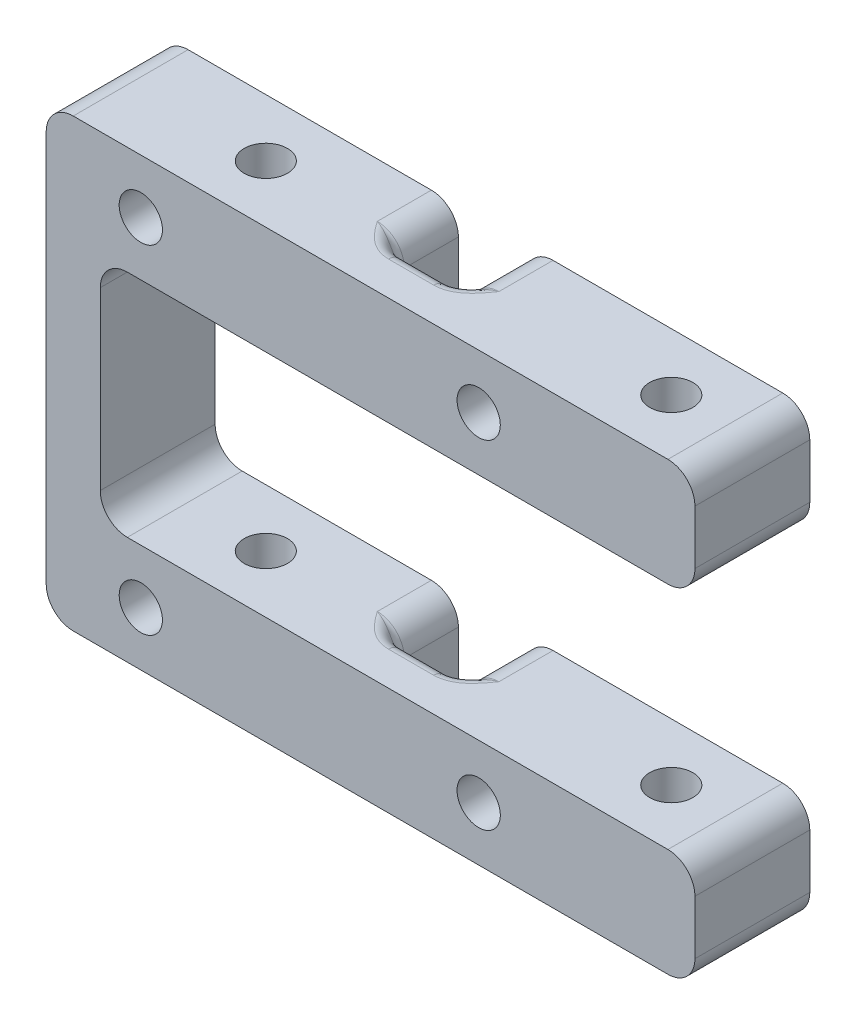
SolidWorks part; units mm, degrees
ref_plane "前视基准面" through (0, 0, 0) normal (0, 0, 1) x (1, 0, 0)
ref_plane "上视基准面" through (0, 0, 0) normal (0, 1, 0) x (1, 0, 0)
ref_plane "右视基准面" through (0, 0, 0) normal (1, 0, 0) x (0, 0, -1)
other "Configuration Table"
sketch "草图1" plane through (0, 0, 0) normal (0, 0, 1) x (1, 0, 0)
  line L1 (0, 0) -> (48, 0)
  line L2 (0, 0) -> (0, 33)
  line L3 (0, 33) -> (48, 33)
  line L4 (48, 0) -> (48, 33)
  dimension "D1" = 48
  dimension "D2" = 33
extrude "凸台-拉伸1" add sketch "草图1" along normal blind 8.5
sketch "草图2" plane through (0, 0, 8.5) normal (0, 0, 1) x (1, 0, 0)
  line L0 (0, 16.5) -> (51.2817, 16.5) construction
  line L1 (0, 33) -> (0, 0) construction
  line L2 (48, 0) -> (48, 33) construction
  line L3 (4, 16.5) -> (48, 16.5)
  line L4 (4, 8) -> (4, 25)
  line L5 (4, 25) -> (48, 25)
  line L6 (48, 8) -> (48, 25)
  line L7 (4, 8) -> (48, 8)
  line M6 (48, 0) -> (48, 33)
  dimension "D1" = 4
  dimension "D2" = 8.5
extrude "切除-拉伸1" cut sketch "草图2" against normal blind 8.5 contours L5 L4 L3 M6 | L4 L7 L3 M6 region at (26, 20.75, 8.5) region at (26, 12.25, 8.5)
sketch "草图3" plane through (0, 0, 0) normal (0, -1, 0) x (1, 0, 0)
  line L0 (0, 4.25) -> (48.3621, 4.25) construction
  line L1 (0, 8.5) -> (0, 0) construction
  circle A0 centre (12, 4.25) radius 1.6
  circle A1 centre (42, 4.25) radius 1.6
  dimension "D1" = 3.2
  dimension "D2" = 3.2
  dimension "D3" = 30
  dimension "D4" = 12
extrude "切除-拉伸2" cut sketch "草图3" against normal blind 48.5
sketch "草图4" plane through (0, 0, 0) normal (0, -1, 0) x (1, 0, 0)
  line L0 (0, 0) -> (48, 0) construction
  line L1 (22, 0) -> (27, 0)
  line L2 (22, 0) -> (22, 5)
  line L3 (22, 5) -> (27, 5)
  line L4 (27, 0) -> (27, 5)
  line L5 (0, 8.5) -> (48, 8.5) construction
  line L7 (48, 8.5) -> (48, 0) construction
  dimension "D1" = 3.5
  dimension "D2" = 5
  dimension "D3" = 21
extrude "切除-拉伸3" cut sketch "草图4" against normal blind 48.5
fillet "圆角1" radius 2 8 edges at (22, 0, 2.5) (27, 0, 2.5) (27, 25, 2.5) (27, 33, 2.5) (22, 25, 2.5) (22, 33, 2.5) (27, 8, 2.5) (22, 8, 2.5)
fillet "圆角2" radius 1 16 edges at (24.5, 33, 5) (24.5, 25, 5) (24.5, 8, 5) (24.5, 0, 5) (27.5858, 32.4142, 5) (27.5858, 25.5858, 5) (21.4142, 32.4142, 5) (21.4142, 25.5858, 5) (27.5858, 7.4142, 5) (27.5858, 0.5858, 5) (21.4142, 7.4142, 5) (21.4142, 0.5858, 5) (27, 29, 5) (22, 29, 5) (27, 4, 5) (22, 4, 5)
fillet "圆角3" radius 2 8 edges at (4, 25, 4.25) (4, 8, 4.25) (48, 8, 4.25) (0, 0, 4.25) (0, 33, 4.25) (48, 33, 4.25) (48, 25, 4.25) (48, 0, 4.25)
sketch "草图5" plane through (0, 0, 8.5) normal (0, 0, 1) x (1, 0, 0)
  line L0 (0, 16.5) -> (50.5462, 16.5) construction
  line L1 (0, 31) -> (0, 2) construction
  circle A0 centre (32, 29) radius 1.6
  circle A1 centre (7, 29) radius 1.6
  circle A2 centre (7, 4) radius 1.6
  circle A3 centre (32, 4) radius 1.6
  dimension "D1" = 3.2
  dimension "D2" = 12.5
  dimension "D4" = 7
  dimension "D3" = 2
extrude "切除-拉伸4" cut sketch "草图5" against normal blind 48.5
